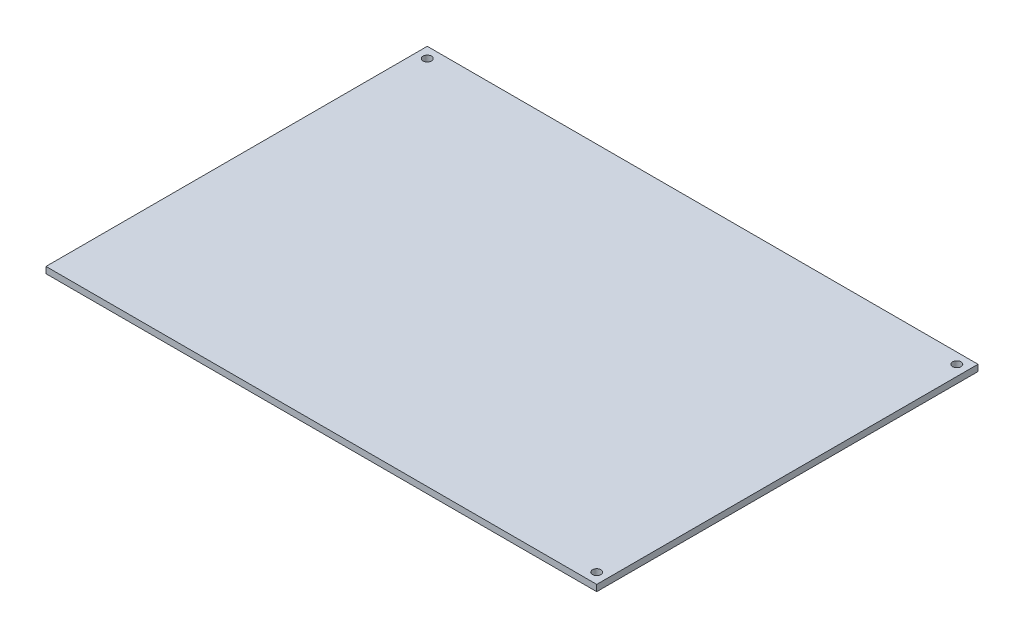
SolidWorks part; units mm, degrees
ref_plane "Front Plane" through (0, 0, 0) normal (0, 0, 1) x (1, 0, 0)
ref_plane "Top Plane" through (0, 0, 0) normal (0, 1, 0) x (1, 0, 0)
ref_plane "Right Plane" through (0, 0, 0) normal (1, 0, 0) x (0, 0, -1)
sketch "Sketch1" plane through (0, 0, 0) normal (0, 1, 0) x (1, 0, 0)
  line L1 (130, 90) -> (-130, 90)
  line L2 (130, 90) -> (130, -90)
  line L3 (130, -90) -> (-130, -90)
  line L4 (-130, 90) -> (-130, -90)
  line L5 (130, 90) -> (-130, -90) construction
  line L6 (130, -90) -> (-130, 90) construction
  point P0 (0, 0)
  dimension "D1" = 180
  dimension "D2" = 260
extrude "Boss-Extrude1" add sketch "Sketch1" along normal blind 3
sketch "Sketch2" plane through (0, 3, 0) normal (0, 1, 0) x (1, 0, 0)
  line L0 (-130, -90) -> (130, -90) construction
  line L1 (130, -90) -> (130, 90) construction
  line L2 (130, 90) -> (-130, -90) construction
  line L3 (0, 90) -> (0, -90) construction
  line L4 (130, 90) -> (-130, 90) construction
  line L5 (-130, 0) -> (130, 0) construction
  line L6 (-130, 90) -> (-130, -90) construction
  circle A0 centre (125, -85) radius 2
  circle A1 centre (125, 85) radius 2
  circle A2 centre (-125, 85) radius 2
  dimension "D1" = 4
  dimension "D2" = 5
  dimension "D3" = 5
extrude "Cut-Extrude1" cut sketch "Sketch2" against normal through all
